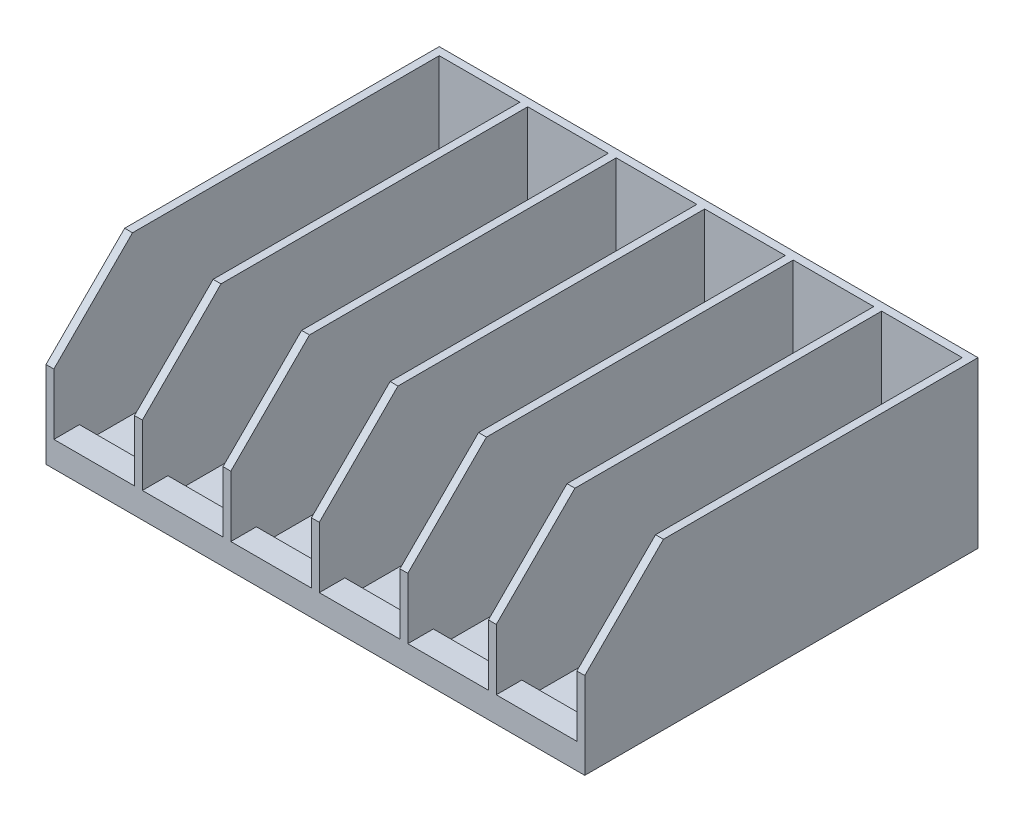
SolidWorks part; units mm, degrees
ref_plane "Front Plane" through (0, 0, 0) normal (0, 0, 1) x (1, 0, 0)
ref_plane "Top Plane" through (0, 0, 0) normal (0, 1, 0) x (1, 0, 0)
ref_plane "Right Plane" through (0, 0, 0) normal (1, 0, 0) x (0, 0, -1)
sketch "Sketch1" plane through (0, 0, 0) normal (0, 1, 0) x (1, 0, 0)
  line L1 (0, 0) -> (137, 0)
  line L2 (0, 0) -> (0, 100)
  line L3 (0, 100) -> (137, 100)
  line L4 (137, 0) -> (137, 100)
  dimension "D1" = 137
  dimension "D2" = 100
extrude "Boss-Extrude1" add sketch "Sketch1" along normal blind 2
sketch "Sketch3" plane through (0, 0, 0) normal (-1, 0, 0) x (0, 0, 1)
  line L0 (-100, 2) -> (-100, 42)
  line L1 (-100, 2) -> (0, 2)
  line L2 (0, 2) -> (0, 22)
  line L3 (0, 22) -> (-20, 42)
  line L4 (-20, 42) -> (-100, 42)
  dimension "D1" = 40
  dimension "D2" = 20
  dimension "D3" = 135
extrude "Boss-Extrude2" add sketch "Sketch3" against normal blind 2
sketch "Sketch4" plane through (0, 0, -100) normal (0, 0, -1) x (-1, 0, 0)
  line L1 (-137, 2) -> (-2, 2)
  line L2 (-137, 2) -> (-137, 42)
  line L3 (-137, 42) -> (-2, 42)
  line L4 (-2, 2) -> (-2, 42)
extrude "Boss-Extrude3" add sketch "Sketch4" against normal blind 2
extrude "Boss-Extrude6" add sketch "Sketch3<5>" against normal blind 2 from offset 22.5 offset against normal yes
sketch "Sketch3<5>" plane through (0, 0, 0) normal (-1, 0, 0) x (0, 0, 1) same geometry as "Sketch3"
extrude "Boss-Extrude7" add sketch "Sketch3<6>" against normal blind 2 from offset 45 offset against normal yes
sketch "Sketch3<6>" plane through (0, 0, 0) normal (-1, 0, 0) x (0, 0, 1) same geometry as "Sketch3"
extrude "Boss-Extrude8" add sketch "Sketch3<7>" against normal blind 2 from offset 67.5 offset against normal yes
sketch "Sketch3<7>" plane through (0, 0, 0) normal (-1, 0, 0) x (0, 0, 1) same geometry as "Sketch3"
extrude "Boss-Extrude9" add sketch "Sketch3<8>" against normal blind 2 from offset 90 offset against normal yes
sketch "Sketch3<8>" plane through (0, 0, 0) normal (-1, 0, 0) x (0, 0, 1) same geometry as "Sketch3"
extrude "Boss-Extrude10" add sketch "Sketch3<9>" against normal blind 2 from offset 112.5 offset against normal yes
sketch "Sketch3<9>" plane through (0, 0, 0) normal (-1, 0, 0) x (0, 0, 1) same geometry as "Sketch3"
extrude "Boss-Extrude11" add sketch "Sketch3<10>" against normal blind 2 from offset 135 offset against normal yes
sketch "Sketch3<10>" plane through (0, 0, 0) normal (-1, 0, 0) x (0, 0, 1) same geometry as "Sketch3"
sketch "Sketch5" plane through (2, 0, 0) normal (1, 0, 0) x (0, 0, -1)
  line L0 (0, 2) -> (0, 6.5)
  line L1 (0, 2) -> (0, 22) construction
  line L2 (0, 6.5) -> (6.5, 6.5)
  line L3 (6.5, 6.5) -> (11, 2)
  line L4 (98, 2) -> (0, 2) construction
  line L5 (11, 2) -> (0, 2)
  dimension "D1" = 4.5
  dimension "D2" = 6.5
  dimension "D3" = 135
extrude "Boss-Extrude12" add sketch "Sketch5" along normal blind 133
